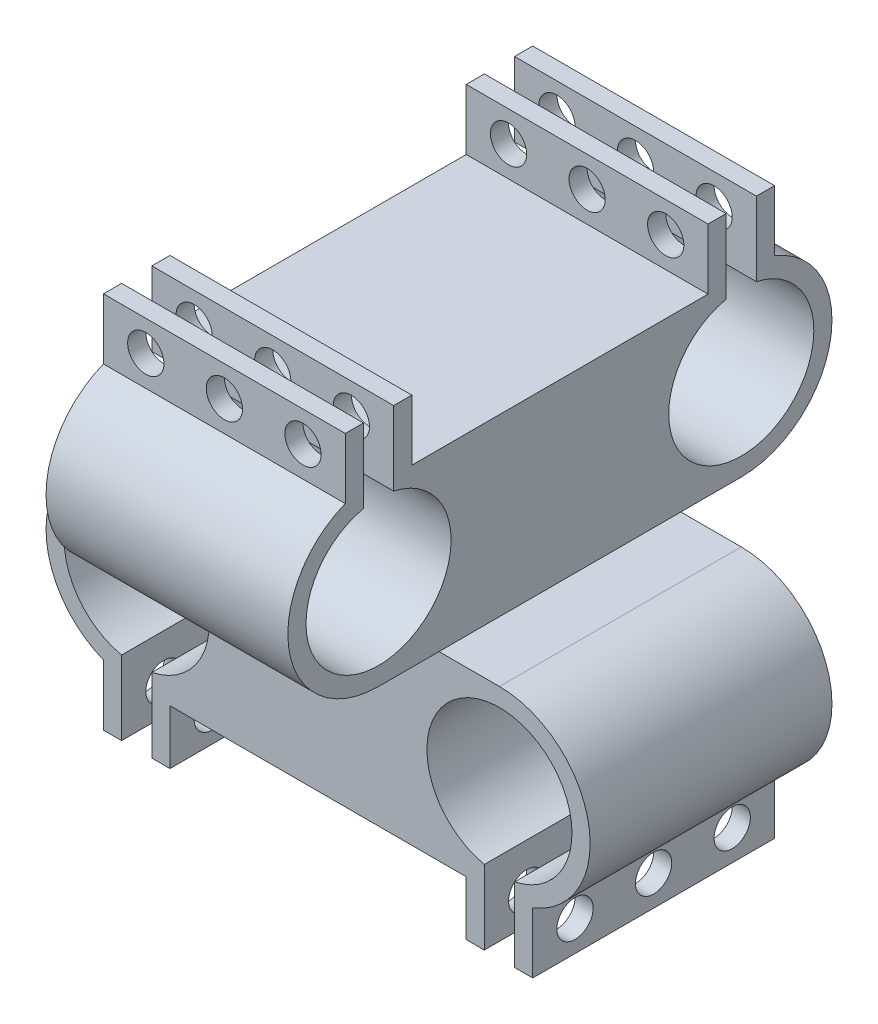
SolidWorks part; units mm, degrees
ref_plane "정면" through (0, 0, 0) normal (0, 0, 1) x (1, 0, 0)
ref_plane "윗면" through (0, 0, 0) normal (0, 1, 0) x (1, 0, 0)
ref_plane "우측면" through (0, 0, 0) normal (1, 0, 0) x (0, 0, -1)
sketch "스케치1" plane through (0, 0, 0) normal (1, 0, 0) x (0, 0, -1)
  line L0 (0, 7.5) -> (0, -7.5) construction
  line L1 (-12.25, 0) -> (12.25, 0) construction
  line L2 (-15, 0) -> (15, 0) construction
  line L3 (-17.75, 12) -> (-16.25, 12)
  line L4 (-17.75, 12) -> (-17.75, 5.3327)
  line L5 (-12.75, 0) -> (12.75, 0) construction
  line L6 (-12.25, 12) -> (-12.25, 5.3327)
  line L7 (-17.75, -0.0455) -> (-12.25, 0) construction
  line L8 (12.25, 12) -> (12.25, 0) construction
  line L9 (12.25, 12) -> (12.25, 5.3327)
  line L10 (17.75, 12) -> (17.75, 5.3327)
  line L11 (17.75, 12) -> (16.25, 12)
  line L12 (-13.75, 10.5) -> (-13.75, 5.8683)
  line L13 (13.75, 10.5) -> (13.75, 1.5) construction
  line L14 (-16.25, 10.5) -> (-16.25, 5.8683)
  line L15 (13.75, 12) -> (12.25, 12)
  line L16 (13.75, 10.5) -> (13.75, 5.8683)
  line L17 (-12.25, 6.9776) -> (12.25, 6.9776)
  line L18 (16.25, 10.5) -> (16.25, 5.8683)
  line L19 (16.25, 10.5) -> (16.25, 1.5) construction
  line L20 (-16.25, 10.5) -> (-16.25, 12)
  line L21 (-13.75, 10.5) -> (-13.75, 12)
  line L22 (13.75, 10.5) -> (13.75, 12)
  line L23 (16.25, 10.5) -> (16.25, 12)
  line L24 (-16.25, 10.5) -> (-13.75, 10.5) construction
  line L25 (-13.75, 12) -> (-12.25, 12)
  line L26 (-17.75, 12) -> (-12.25, 12) construction
  line L27 (16.25, 10.5) -> (13.75, 10.5) construction
  line L28 (17.75, 12) -> (12.25, 12) construction
  line L29 (-15, -7.5) -> (15, -7.5)
  line L30 (17.75, 12) -> (17.75, 0) construction
  line L31 (-17.75, 12) -> (-17.75, -0.0455) construction
  line L33 (-16.25, 10.5) -> (-16.25, 1.467) construction
  line L35 (-13.75, 10.5) -> (-13.75, 1.4876) construction
  line L36 (-12.25, 12) -> (-12.25, 0) construction
  line L37 (-16.25, 1.467) -> (-13.75, 1.4876) construction
  line L38 (16.25, 1.5) -> (13.75, 1.5) construction
  line L39 (17.75, 0) -> (12.25, 0) construction
  arc A0 (-16.25, 5.8683) -> (-13.75, 5.8683) centre (-15, 0) ccw
  arc A1 (16.25, 5.8683) -> (13.75, 5.8683) centre (15, 0) cw
  arc A2 (-16.25, 7.3951) -> (-13.75, 7.3951) centre (-15, 0) ccw
  arc A3 (16.25, 7.3951) -> (13.75, 7.3951) centre (15, 0) cw
  circle A4 centre (-15, 0) radius 6 construction
  circle A5 centre (-15, 0) radius 7.5 construction
  point P3 (0, 0)
  point P12 (-15, 6)
  dimension "D1" = 12
  dimension "D2" = 30
  dimension "D4" = 12
  dimension "D5" = 5.5
  dimension "D7" = 6.6673
  dimension "D3" = 1.5
  dimension "D6" = 1.5
extrude "보스-돌출1" add sketch "스케치1" along normal blind 20 contours L29 A3 L17 A2 | L4 A2 L6 A0 | L6 A2 L12 A0 | L14 A2 L4 A0 | A2 L14 L20 L3 L4 | A2 L6 L25 L21 L12 | A3 L10 A1 L9 | A3 L18 A1 L10 | L18 A3 L10 L11 L23 | L9 A3 L16 L22 L15 | A3 L9 A1 L16 region at (0, 9.6057, 17.0109) region at (0, 6.4233, 17.0093) region at (0, 6.1552, 17.9585) region at (0, -0.3836, 0) region at (0, 6.4233, 12.9907) region at (0, -1.3607, -7.8366) region at (0, 9.6057, 12.9891) region at (0, 6.4233, -12.9907) region at (0, 9.6057, -12.9891) region at (0, 9.6057, -17.0109) region at (0, 6.4233, -17.0093)
sketch "스케치2" plane through (0, 0, 17.75) normal (0, 0, 1) x (1, 0, 0)
  line L0 (0, 9.4888) -> (20, 9.4888) construction
  line L1 (10, 12) -> (10, 6.9776) construction
  line L2 (3.5, 12) -> (3.5, 6.9776) construction
  line L3 (16.5, 12) -> (16.5, 6.9776) construction
  line L4 (0, 12) -> (0, 6.9776)
  line L5 (0, 6.9776) -> (20, 6.9776)
  line L6 (20, 6.9776) -> (20, 12)
  line L7 (20, 12) -> (0, 12)
  line L8 (0, 12) -> (0, 6.9776)
  line L9 (0, 6.9776) -> (20, 6.9776)
  line L10 (20, 6.9776) -> (20, 12)
  line L11 (20, 12) -> (0, 12)
  circle A0 centre (3.5, 9.4888) radius 1.5
  circle A1 centre (16.5, 9.4888) radius 1.5
  circle A2 centre (10, 9.4888) radius 1.5
  point P14 (3.5, 9.4888)
  point P17 (16.5, 9.4888)
  dimension "D3" = 3
  dimension "D2" = 6.5
  dimension "D1" = 0
extrude "컷-돌출1" cut sketch "스케치2" against normal through all contours A0 | A2 | A1 region at (3.5, 9.4888, 17.75) region at (10, 9.4888, 17.75)
sketch "스케치5" plane through (0, 0, 0) normal (0, 0, 1) x (1, 0, 0)
  line L0 (-72.0207, -10.4098) -> (-72.0207, -25.4098) construction
  line L1 (-84.2707, -17.9098) -> (-59.7707, -17.9098) construction
  line L2 (-87.0207, -17.9098) -> (-57.0207, -17.9098) construction
  line L3 (-89.7707, -5.9098) -> (-88.2707, -5.9098)
  line L4 (-89.7707, -5.9098) -> (-89.7707, -12.5771)
  line L5 (-84.7707, -17.9098) -> (-59.2707, -17.9098) construction
  line L6 (-84.2707, -5.9098) -> (-84.2707, -12.5771)
  line L7 (-59.7707, -5.9098) -> (-59.7707, -12.5771)
  line L8 (-54.2707, -5.9098) -> (-54.2707, -12.5771)
  line L9 (-54.2707, -5.9098) -> (-55.7707, -5.9098)
  line L10 (-85.7707, -7.4098) -> (-85.7707, -12.0415)
  line L11 (-88.2707, -7.4098) -> (-88.2707, -12.0415)
  line L12 (-58.2707, -5.9098) -> (-59.7707, -5.9098)
  line L13 (-58.2707, -7.4098) -> (-58.2707, -12.0415)
  line L14 (-84.2707, -10.9322) -> (-59.7707, -10.9322)
  line L15 (-55.7707, -7.4098) -> (-55.7707, -12.0415)
  line L16 (-88.2707, -7.4098) -> (-88.2707, -5.9098)
  line L17 (-85.7707, -7.4098) -> (-85.7707, -5.9098)
  line L18 (-58.2707, -7.4098) -> (-58.2707, -5.9098)
  line L19 (-55.7707, -7.4098) -> (-55.7707, -5.9098)
  line L20 (-85.7707, -5.9098) -> (-84.2707, -5.9098)
  line L21 (-87.0207, -25.4098) -> (-57.0207, -25.4098)
  line L22 (20, -7.5) -> (0, -7.5) construction
  line L23 (25, -7.5) -> (-5, -7.5)
  line L24 (25, -7.5) -> (25, -22.5) construction
  line L25 (25, -22.5) -> (-5, -22.5)
  line L26 (-5, -7.5) -> (-5, -22.5) construction
  line L27 (20, -7.5) -> (0, -7.5)
  line L28 (-2.25, -20.3327) -> (-2.25, -27.0027)
  line L29 (-7.75, -20.3327) -> (-6.25, -20.3327)
  line L30 (-7.75, -20.3327) -> (-7.75, -27.0027)
  line L31 (-7.75, -27.0027) -> (-6.25, -27.0027)
  line L32 (-6.25, -20.3327) -> (-6.25, -27.0027)
  line L33 (-2.25, -20.3327) -> (-3.75, -20.3327)
  line L34 (-3.75, -20.3327) -> (-3.75, -27.0027)
  line L35 (-2.25, -27.0027) -> (-3.75, -27.0027)
  line L36 (10, -7.5) -> (10, -22.5) construction
  line L37 (22.25, -20.3327) -> (23.75, -20.3327)
  line L38 (27.75, -20.3327) -> (26.25, -20.3327)
  line L39 (27.75, -20.3327) -> (27.75, -27.0027)
  line L40 (22.25, -20.3327) -> (22.25, -27.0027)
  line L41 (23.75, -20.3327) -> (23.75, -27.0027)
  line L42 (26.25, -20.3327) -> (26.25, -27.0027)
  line L43 (22.25, -27.0027) -> (23.75, -27.0027)
  line L44 (27.75, -27.0027) -> (26.25, -27.0027)
  arc A0 (-88.2707, -12.0415) -> (-85.7707, -12.0415) centre (-87.0207, -17.9098) ccw
  arc A1 (-55.7707, -12.0415) -> (-58.2707, -12.0415) centre (-57.0207, -17.9098) cw
  arc A2 (-88.2707, -10.5147) -> (-85.7707, -10.5147) centre (-87.0207, -17.9098) ccw
  arc A3 (-55.7707, -10.5147) -> (-58.2707, -10.5147) centre (-57.0207, -17.9098) cw
  circle A4 centre (-5, -15) radius 7.5
  circle A5 centre (25, -15) radius 7.5
  circle A6 centre (-5, -15) radius 6
  circle A7 centre (25, -15) radius 6
  point P2 (-72.0207, -17.9098)
  point P11 (-87.0207, -11.9098)
  point P44 (10, -7.5)
  point P47 (10, -7.5)
  point P72 (-7.75, -21.9776)
  point P73 (-6.25, -19.1657)
  point P74 (-3.75, -22.3951)
  point P75 (-2.25, -21.4476)
  point P76 (22.25, -21.9776)
  point P77 (23.75, -22.3951)
  point P78 (26.25, -22.3951)
  point P79 (27.75, -21.9776)
  dimension "D4" = 6
  dimension "D5" = 7.5
  dimension "D10" = 12
  dimension "D1" = 24.5
  dimension "D2" = 30
  dimension "D3" = 30
  dimension "D6" = 6.6673
  dimension "D7" = 1.5
  dimension "D8" = 30
  dimension "D9" = 15
  dimension "D11" = 1.5
  dimension "D12" = 6.67
  dimension "D13" = 2.5
  dimension "D14" = 2.5
extrude "보스-돌출2" add sketch "스케치5" along normal mid plane 20 contours A7 L39 A5 L40 | A7 L40 A5 L41 | A7 L42 A5 L39 | A5 L42 L44 L39 | A5 L40 L25 L41 | L40 L43 L41 L25 | A5 L23 A4 L28 L25 L40 | A6 L28 A4 L30 | A6 L30 A4 L32 | A4 L30 L31 L32 | A4 L34 L25 L28 | L35 L28 L25 L34 | A6 L34 A4 L28 region at (10, -14.9745, 0) region at (30.1559, -9.8441, 0) region at (22.8177, -22.3316, 0) region at (22.9907, -21.4233, 0) region at (27.0093, -21.4233, 0) region at (27.0109, -24.607, 0) region at (23, -24.7513, 0) region at (0.1559, -9.8441, 0) region at (-3, -24.7513, 0) region at (-2.8177, -22.3316, 0) region at (-7.0109, -24.607, 0) region at (-7.0093, -21.4233, 0) region at (-2.9907, -21.4233, 0)
sketch "스케치6" plane through (27.75, 0, 0) normal (1, 0, 0) x (0, 0, -1)
  line L0 (0, 0) -> (0, -27.0027) construction
  line L1 (-10, -24.4902) -> (10, -24.4902) construction
  line L4 (10, -27.0027) -> (10, -21.9776)
  line L5 (10, -21.9776) -> (-10, -21.9776)
  line L6 (-10, -21.9776) -> (-10, -27.0027)
  line L7 (-10, -27.0027) -> (10, -27.0027)
  line L8 (10, -27.0027) -> (10, -21.9776)
  line L9 (10, -21.9776) -> (-10, -21.9776)
  line L10 (-10, -21.9776) -> (-10, -27.0027)
  line L11 (-10, -27.0027) -> (10, -27.0027)
  circle A0 centre (-6.5, -24.4902) radius 1.5
  circle A1 centre (6.5, -24.4902) radius 1.5
  circle A2 centre (0, -24.4902) radius 1.5
  dimension "D3" = 3
  dimension "D2" = 6.5
  dimension "D1" = 0
extrude "컷-돌출2" cut sketch "스케치6" against normal through all contours A0 | A2 | A1 region at (27.75, -24.4902, 6.5) region at (27.75, -24.4902, -6.5) region at (27.75, -24.4902, 0)
